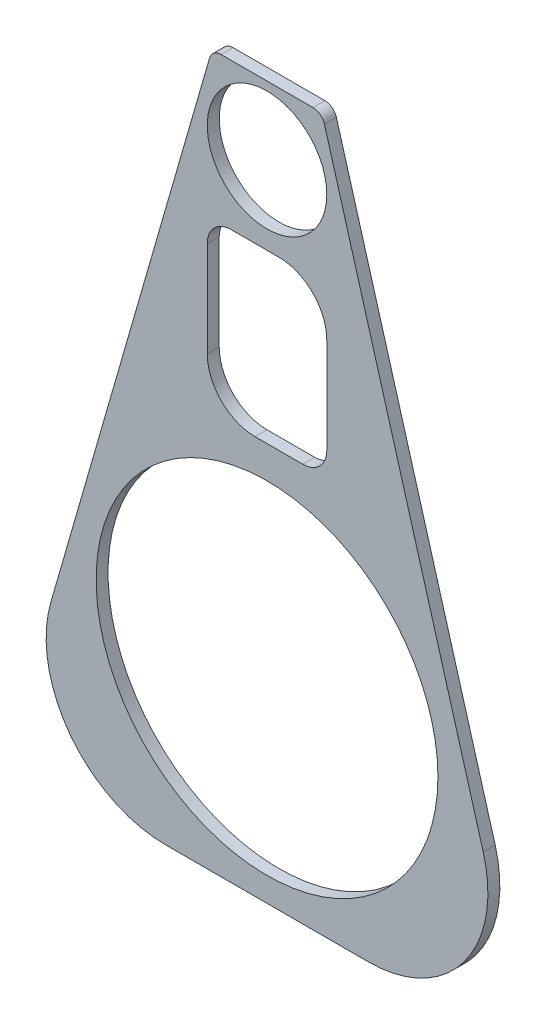
SolidWorks part; units mm, degrees
material "6061 Alloy"
ref_plane "Front" through (0, 0, 0) normal (0, 0, 1) x (1, 0, 0)
ref_plane "Top" through (0, 0, 0) normal (0, 1, 0) x (1, 0, 0)
ref_plane "Right" through (0, 0, 0) normal (1, 0, 0) x (0, 0, -1)
sketch "Sketch3" plane through (0, 0, 0) normal (0, 0, 1) x (1, 0, 0)
  line L1 (969.886, -1066.4574) -> (305.5143, 1238.3736)
  line L3 (-174.8832, 1238.3736) -> (-839.2549, -1066.4574)
  line L4 (65.3155, 1274.5248) -> (65.3155, -1694.2708) construction
  line L17 (-126.8393, 1274.5248) -> (257.4704, 1274.5248)
  line L19 (15.3155, -38.8919) -> (215.3155, -38.8919)
  line L20 (-184.6845, 161.1081) -> (-184.6845, 561.1081)
  line L21 (-84.6845, 661.1081) -> (115.3155, 661.1081)
  line L22 (315.3155, 61.1081) -> (315.3155, 461.1081)
  line L23 (-358.8163, -1704.9447) -> (489.4474, -1704.9447)
  line L24 (-184.6845, -38.8919) -> (315.3155, 661.1081) construction
  line L25 (-184.6845, 661.1081) -> (315.3155, -38.8919) construction
  arc A10 (-174.8832, 1238.3736) -> (-126.8393, 1274.5248) centre (-126.8393, 1224.5248) cw
  arc A11 (305.5143, 1238.3736) -> (257.4704, 1274.5248) centre (257.4704, 1224.5248) ccw
  circle A13 centre (65.3155, 988.5365) radius 250
  circle A14 centre (65.3155, -888.8919) radius 715
  arc A15 (-839.2549, -1066.4574) -> (-358.8163, -1704.9447) centre (-358.8163, -1204.9447) ccw
  arc A16 (489.4474, -1704.9447) -> (969.886, -1066.4574) centre (489.4474, -1204.9447) ccw
  arc A17 (-184.6845, 161.1081) -> (15.3155, -38.8919) centre (15.3155, 161.1081) ccw
  arc A18 (315.3155, 461.1081) -> (115.3155, 661.1081) centre (115.3155, 461.1081) ccw
  arc A19 (-184.6845, 561.1081) -> (-84.6845, 661.1081) centre (-84.6845, 561.1081) cw
  arc A20 (215.3155, -38.8919) -> (315.3155, 61.1081) centre (215.3155, 61.1081) ccw
  point P1 (65.3155, 311.1081)
  point P11 (60.2939, 331.5151)
  point P28 (-164.4625, 1274.5248)
  point P33 (295.0936, 1274.5248)
  dimension "D4" = 500
  dimension "D5" = 700
  dimension "D6" = 500
  dimension "D7" = 500
  dimension "D8" = 500
  dimension "D9" = 50
  dimension "D11" = 50
  dimension "D2" = 1430
  dimension "D10" = 200
  dimension "D12" = 200
  dimension "D13" = 100
  dimension "D14" = 100
  dimension "D3" = 1200
  dimension "D15" = 820
  dimension "D16" = 820
  dimension "D17" = 300
  dimension "D18" = 300
extrude "Boss-Extrude1" add sketch "Sketch3" along normal blind 50 contours L3 L1 region at (860.9581, -1484.4931, 0)
